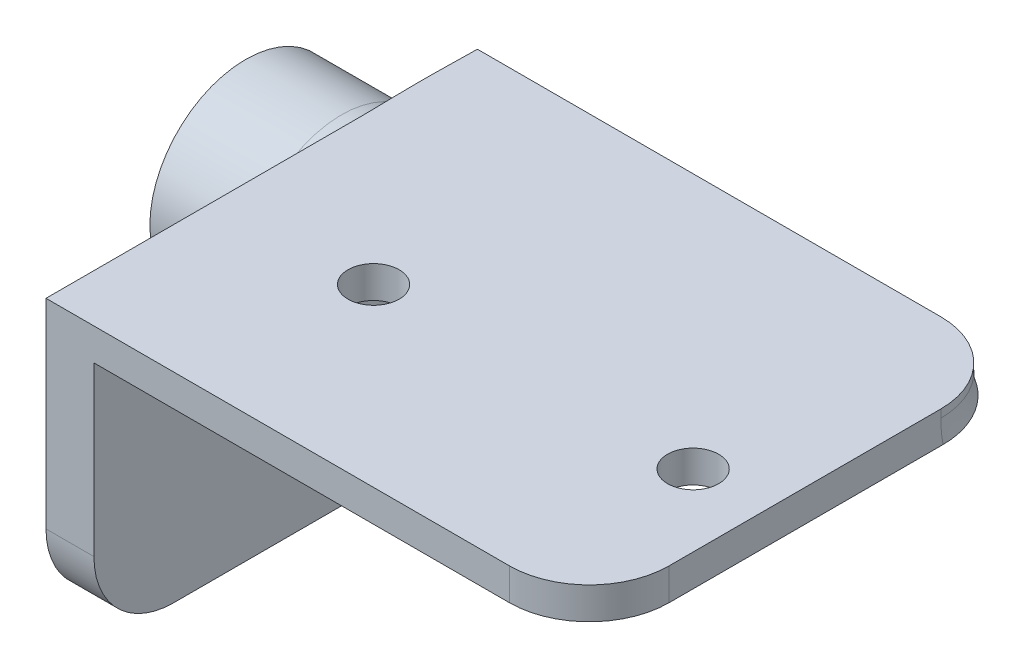
SolidWorks part; units mm, degrees
ref_plane "Alzado" through (0, 0, 0) normal (0, 0, 1) x (1, 0, 0)
ref_plane "Planta" through (0, 0, 0) normal (0, 1, 0) x (1, 0, 0)
ref_plane "Vista lateral" through (0, 0, 0) normal (1, 0, 0) x (0, 0, -1)
sketch "Croquis1" plane through (0, 0, 0) normal (0, 1, 0) x (1, 0, 0)
  line L1 (0, 0) -> (34, 0)
  line L2 (0, 0) -> (0, -20)
  line L3 (0, -20) -> (34, -20)
  line L4 (34, 0) -> (34, -20)
  dimension "D1" = 34
  dimension "D2" = 20
extrude "Saliente-Extruir1" add sketch "Croquis1" along normal blind 3.5
sketch "Croquis2" plane through (0, 3.5, 0) normal (0, 1, 0) x (1, 0, 0)
  line L0 (0, 0) -> (0, -20) construction
  line L1 (0, -20) -> (34, -20) construction
  circle A0 centre (9.5, -9) radius 1.6
  circle A1 centre (29.5, -9) radius 1.6
  dimension "D1" = 3.2
  dimension "D2" = 3.2
  dimension "D3" = 20
  dimension "D4" = 9.5
  dimension "D5" = 11
extrude "Cortar-Extruir1" cut sketch "Croquis2" against normal up to surface (3.5 mm away) up to face at (17, 0, 10)
sketch "Croquis3" plane through (0, 0, 0) normal (0, -1, 0) x (1, 0, 0)
  line L0 (0, 20) -> (34, 20) construction
  line L1 (0, 0) -> (3, 0)
  line L2 (0, 0) -> (0, 20)
  line L3 (0, 20) -> (3, 20)
  line L4 (3, 0) -> (3, 20)
  dimension "D1" = 3
extrude "Saliente-Extruir2" add sketch "Croquis3" along normal blind 20
sketch "Croquis4" plane through (0, 0, 0) normal (0, 0, -1) x (-1, 0, 0)
  line L0 (-3, -20) -> (-3, 0) construction
  line L1 (-3, -1.5) -> (0, -1.5)
  line L2 (-3, -1.5) -> (-3, -15.5)
  line L3 (-3, -15.5) -> (0, -15.5)
  line L4 (0, -1.5) -> (0, -15.5)
  line L5 (0, 3.5) -> (0, -20) construction
  line L6 (-34, 3.5) -> (0, 3.5) construction
  dimension "D1" = 14
  dimension "D2" = 5
extrude "Saliente-Extruir3" add sketch "Croquis4" along normal blind 10
sketch "Croquis5" plane through (0, 0, 0) normal (-1, 0, 0) x (0, 0, 1)
  line L0 (-10, -15.5) -> (0, -15.5) construction
  line L1 (0, 3.5) -> (0, -1.5) construction
  circle A0 centre (-3.5, -8.3) radius 6
  dimension "D1" = 12
  dimension "D2" = 7.2
  dimension "D3" = 3.5
extrude "Saliente-Extruir4" add sketch "Croquis5" along normal blind 11
sketch "Croquis6" plane through (-11, 0, 0) normal (-1, 0, 0) x (0, 0, 1)
  circle A0 centre (-3.5, -8.3) radius 1.5
  dimension "D1" = 3
extrude "Cortar-Extruir2" cut sketch "Croquis6" against normal up to surface (14 mm away) up to face at (3, -9.25, 2.5)
sketch "Croquis7" plane through (3, 0, 0) normal (1, 0, 0) x (0, 0, -1)
  line L0 (10, -1.5) -> (10, -15.5) construction
  line L1 (7.1, -12.9) -> (0.8, -12.9)
  line L2 (7.1, -12.9) -> (7.1, -4.6)
  line L3 (7.1, -4.6) -> (0.8, -4.6)
  line L4 (0.8, -12.9) -> (0.8, -4.6)
  line L5 (10, -15.5) -> (0, -15.5) construction
  dimension "D1" = 8.3
  dimension "D2" = 6.3
  dimension "D3" = 2.9
  dimension "D4" = 2.6
extrude "Cortar-Extruir3" cut sketch "Croquis7" against normal blind 6.4
sketch "Croquis8" plane through (-11, 0, 0) normal (-1, 0, 0) x (0, 0, 1)
  circle A0 centre (-3.5, -8.3) radius 4.2
  dimension "D1" = 8.4
extrude "Cortar-Extruir4" cut sketch "Croquis8" against normal blind 6.3
fillet "Redondeo1" radius 1 1 edges at (-3.4, -8.3, -5)
sketch "Croquis9" plane through (3, 0, 0) normal (1, 0, 0) x (0, 0, -1)
  line L0 (-20, -20) -> (-20, 0) construction
  line L1 (0, -20) -> (-20, -20)
  line L2 (0, -20) -> (0, -15.5)
  line L3 (0, -15.5) -> (-20, -15.5)
  line L4 (-20, -20) -> (-20, -15.5)
  line L5 (10, -15.5) -> (0, -15.5) construction
  point P7 (0, -14.9153)
extrude "Cortar-Extruir5" cut sketch "Croquis9" against normal up to surface (3 mm away) up to face at (0, -8.3, -9.5)
sketch "Croquis11" plane through (0, 0, 0) normal (0, 0, -1) x (-1, 0, 0)
  line L6 (-3, -1.5) -> (0, -1.5)
  line L7 (0, -1.5) -> (0, 3.5)
  line L8 (0, 3.5) -> (-34, 3.5)
  line L9 (-34, 3.5) -> (-34, 0)
  line L10 (-34, 0) -> (-3, 0)
  line L11 (-3, 0) -> (-3, -1.5)
  line L12 (-3, -1.5) -> (0, -1.5)
  line L13 (0, -1.5) -> (0, 3.5)
  line L14 (0, 3.5) -> (-34, 3.5)
  line L15 (-34, 3.5) -> (-34, 0)
  line L16 (-34, 0) -> (-3, 0)
  line L17 (-3, 0) -> (-3, -1.5)
  dimension "D1" = 0
extrude "Saliente-Extruir5" add sketch "Croquis11" along normal blind 7
fillet "Redondeo5" radius 3 1 edges at (1.5, -1.5, -7)
fillet "Redondeo6" radius 5 5 edges at (34, 0.7235, -7.1022) (34, 1.75, 20) (34, 2.5, -7) (1.5, -15.5, 20) (1.5, -15.5, -10)
sketch "Croquis12" plane through (0, 3.5, 0) normal (0, 1, 0) x (1, 0, 0)
  line L4 (0, -20) -> (29, -20)
  line L5 (34, -15) -> (34, 2)
  line L6 (29, 7) -> (0, 7)
  line L7 (0, 7) -> (0, -20)
  line L8 (0, -20) -> (29, -20)
  line L9 (34, -15) -> (34, 2)
  line L10 (29, 7) -> (0, 7)
  line L11 (0, 7) -> (0, -20)
  circle A0 centre (9.5, -9) radius 1.6 construction
  circle A1 centre (9.5, -9) radius 1.6
  arc A2 (29, -20) -> (34, -15) centre (29, -15) ccw
  arc A3 (34, 2) -> (29, 7) centre (29, 2) ccw
  arc A4 (29, -20) -> (34, -15) centre (29, -15) ccw
  arc A5 (34, 2) -> (29, 7) centre (29, 2) ccw
  circle A6 centre (29.5, -9) radius 1.6 construction
  circle A7 centre (29.5, -9) radius 1.6
  dimension "D1" = 0
extrude "Cortar-Extruir6" cut sketch "Croquis12" against normal blind 1.5
fillet "Redondeo7" radius 5 1 edges at (0, -8.3, -9.5)
